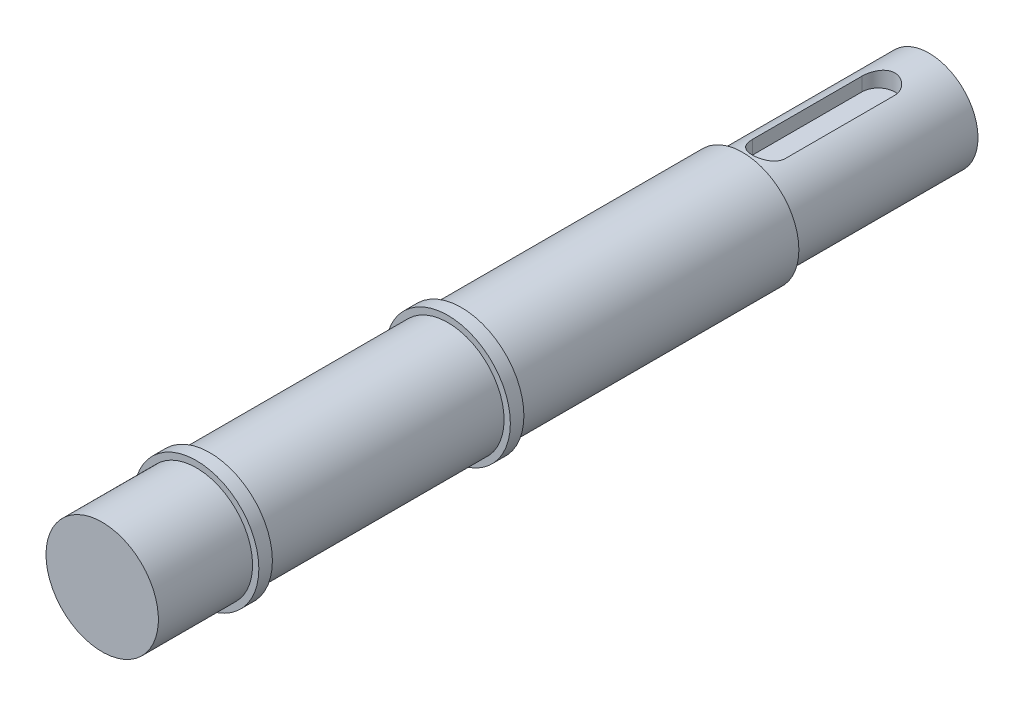
SolidWorks part; units mm, degrees
ref_plane "前视基准面" through (0, 0, 0) normal (0, 0, 1) x (1, 0, 0)
ref_plane "上视基准面" through (0, 0, 0) normal (0, 1, 0) x (1, 0, 0)
ref_plane "右视基准面" through (0, 0, 0) normal (1, 0, 0) x (0, 0, -1)
sketch "草图1" plane through (0, 0, 0) normal (0, 0, 1) x (1, 0, 0)
  circle A0 centre (0, 0) radius 9.45
  circle A1 centre (0, 0) radius 7.4
  circle A2 centre (0, 0) radius 2.7664
  circle A3 centre (0, 0) radius 8.5
  circle A4 centre (0, 0) radius 8.5
  dimension "D1" = 18.9
  dimension "D2" = 14.8
  dimension "D3" = 17
  dimension "D4" = 5.5328
  dimension "D5" = 17
extrude "凸台-拉伸1" add sketch "草图1" along normal blind 28.2 contours A1
extrude "凸台-拉伸2" add sketch "草图1<5>" along normal blind 42.55 from offset 28.2 contours A3
sketch "草图1<5>" plane through (0, 0, 0) normal (0, 0, 1) x (1, 0, 0) same geometry as "草图1"
extrude "凸台-拉伸3" add sketch "草图1<7>" along normal blind 2.05 from offset 70.75 contours A0
sketch "草图1<7>" plane through (0, 0, 0) normal (0, 0, 1) x (1, 0, 0) same geometry as "草图1"
extrude "凸台-拉伸4" add sketch "草图1<8>" along normal blind 2.05 from offset 108.8 separate body contours A0
sketch "草图1<8>" plane through (0, 0, 0) normal (0, 0, 1) x (1, 0, 0) same geometry as "草图1"
extrude "凸台-拉伸5" add sketch "草图1<9>" along normal blind 36 from offset 72.8 contours A4
sketch "草图1<9>" plane through (0, 0, 0) normal (0, 0, 1) x (1, 0, 0) same geometry as "草图1"
extrude "凸台-拉伸6" add sketch "草图1<10>" along normal blind 14.25 from offset 110.85 contours A3
sketch "草图1<10>" plane through (0, 0, 0) normal (0, 0, 1) x (1, 0, 0) same geometry as "草图1"
sketch "草图11" plane through (0, 0, 0) normal (0, 1, 0) x (1, 0, 0)
  line L0 (0, -7.68) -> (0, -24.22) construction
  line L1 (2.5, -7.68) -> (2.5, -24.22)
  line L2 (-2.5, -7.68) -> (-2.5, -24.22)
  arc A0 (2.5, -7.68) -> (-2.5, -7.68) centre (0, -7.68) ccw
  arc A1 (-2.5, -24.22) -> (2.5, -24.22) centre (0, -24.22) ccw
  point P2 (0, -15.95)
  point P8 (0, -5.18)
  point P9 (0, -26.72)
  dimension "D1" = 5.18
  dimension "D2" = 5
  dimension "D3" = 21.54
extrude "切除-拉伸1" cut sketch "草图11" against normal blind 2.5 from offset 7.4
sketch "草图8" plane through (0, 0, 0) normal (0, 0, 1) x (1, 0, 0)
  spline S0 degree 4 poles (11.2763, 0) (11.2815, 0.0001) (11.2959, 0.0006) (11.3231, 0.0026) (11.3674, 0.0073) (11.4237, 0.0155) (11.4962, 0.0286) (11.5812, 0.0473) (11.6741, 0.0711) (11.7745, 0.1005) (11.874, 0.1331) (11.9726, 0.1684) (12.0702, 0.2063) (12.1875, 0.2551) (12.3271, 0.318) (12.4883, 0.3976) (12.6687, 0.495) (12.8498, 0.6019) (13.0256, 0.7132) (13.2003, 0.8326) (13.3672, 0.9531) (13.5373, 1.0851) (13.6926, 1.2106) (13.8627, 1.3587) (13.9988, 1.4805) (14.174, 1.6489) (14.2762, 1.7507) (14.3942, 1.8725) (14.4457, 1.928) (14.4775, 1.9621) knots 0 0 0 0 0 0.005377 0.015084 0.028532 0.04661 0.064855 0.092111 0.119476 0.146842 0.174209 0.201575 0.228941 0.256307 0.307035 0.361767 0.4165 0.471232 0.525964 0.580697 0.635429 0.690161 0.744894 0.799626 0.854358 0.909091 0.954545 1 1 1 1 1 construction
  spline S1 degree 4 poles (11.2763, 0) (11.2815, 0.0001) (11.2959, 0.0006) (11.3231, 0.0026) (11.3674, 0.0073) (11.4237, 0.0155) (11.4962, 0.0286) (11.5812, 0.0473) (11.6741, 0.0711) (11.7745, 0.1005) (11.874, 0.1331) (11.9726, 0.1684) (12.0702, 0.2063) (12.1875, 0.2551) (12.3271, 0.318) (12.4883, 0.3976) (12.6687, 0.495) (12.8498, 0.6019) (13.0256, 0.7132) (13.2003, 0.8326) (13.3672, 0.9531) (13.5373, 1.0851) (13.6926, 1.2106) (13.8627, 1.3587) (13.9988, 1.4805) (14.1361, 1.6124) (14.2023, 1.6775) (14.236, 1.7111) knots 0 0 0 0 0 0.005377 0.015084 0.028532 0.04661 0.064855 0.092111 0.119476 0.146842 0.174209 0.201575 0.228941 0.256307 0.307035 0.361767 0.4165 0.471232 0.525964 0.580697 0.635429 0.690161 0.744894 0.799626 0.854358 0.909091 0.909091 0.909091 0.909091 0.909091
sketch "草图6" plane through (0, 0, 0) normal (0, 0, 1) x (1, 0, 0)
  line L0 (0, 0) -> (14.6649, 2.1549) construction
  circle A0 centre (0, 0) radius 9.45 construction
  circle A1 centre (0, 0) radius 7.4
  circle A2 centre (0, 0) radius 2.7664
  circle A3 centre (0, 0) radius 8.5
  circle A4 centre (0, 0) radius 12 construction
  circle A5 centre (0, 0) radius 9.5 construction
  circle A6 centre (0, 0) radius 11.2763
  circle A7 centre (0, 0) radius 14
  arc A8 (11.7916, 0.1066) -> (11.2614, -0.5791) centre (12.0204, -0.6181) ccw
  spline S0 degree 4 poles (-14.1478, 1999.7229) (9.4338, 23.2482) (10.0756, 0.3378) (10.7357, -0.0602) (11.3674, 0.0073) (11.4237, 0.0155) (11.4962, 0.0286) (11.5812, 0.0473) (11.6741, 0.0711) (11.7745, 0.1005) (11.874, 0.1331) (11.9726, 0.1684) (12.0702, 0.2063) (12.1875, 0.2551) (12.3271, 0.318) (12.4883, 0.3976) (12.6687, 0.495) (12.8498, 0.6019) (13.0256, 0.7132) (13.2003, 0.8326) (13.3672, 0.9531) (13.5373, 1.0851) (13.6926, 1.2106) (13.8627, 1.3587) (14.6115, 2.0283) (17.0468, 4.6575) (-19.889, -31.9248) (1427.9155, 1416.391) knots -0.617559 -0.617559 -0.617559 -0.617559 -0.617559 0.005377 0.015084 0.028532 0.04661 0.064855 0.092111 0.119476 0.146842 0.174209 0.201575 0.228941 0.256307 0.307035 0.361767 0.4165 0.471232 0.525964 0.580697 0.635429 0.690161 0.744894 0.799626 0.854358 1.894324 1.894324 1.894324 1.894324 1.894324 only from (11.2763, 0) to (14.236, 1.7111) construction
  spline S1 degree 4 poles (11.7916, 0.1066) (11.8247, 0.117) (11.8825, 0.1361) (11.9646, 0.1653) (12.0702, 0.2063) (12.1875, 0.2551) (12.3271, 0.318) (12.4883, 0.3976) (12.6687, 0.495) (12.8498, 0.6019) (13.0256, 0.7132) (13.2003, 0.8326) (13.3672, 0.9531) (13.5373, 1.0851) (13.6917, 1.2099) (13.8183, 1.3201) (13.8915, 1.3848) (13.928, 1.4178) knots 0.137896 0.137896 0.137896 0.137896 0.137896 0.174209 0.201575 0.228941 0.256307 0.307035 0.361767 0.4165 0.471232 0.525964 0.580697 0.635429 0.690161 0.744894 0.798429 0.798429 0.798429 0.798429 0.798429
  point P2 (33.674, -7.0096)
  point P11 (12.1017, 0.1374)
  point P12 (11.8725, 1.7446)
  point P19 (13.928, 1.4178)
  point P23 (11.9987, 0.1788)
  dimension "D10" = 0.76
  dimension "D9" = 1.5708
  dimension "D1" = 18.9
  dimension "D2" = 14.8
  dimension "D3" = 17
  dimension "D4" = 5.5328
  dimension "D6" = 28
  dimension "D7" = 19
  dimension "D8" = 22.5526
  dimension "D5" = 24
sketch "草图5" plane through (0, 0, 0) normal (0, 0, 1) x (1, 0, 0)
  spline S0 degree 4 poles (11.2763, 0) (11.2815, 0.0001) (11.2959, 0.0006) (11.3231, 0.0026) (11.3674, 0.0073) (11.4237, 0.0155) (11.4962, 0.0286) (11.5812, 0.0473) (11.6741, 0.0711) (11.7745, 0.1005) (11.874, 0.1331) (11.9726, 0.1684) (12.0702, 0.2063) (12.1875, 0.2551) (12.3271, 0.318) (12.4883, 0.3976) (12.6687, 0.495) (12.8498, 0.6019) (13.0256, 0.7132) (13.2003, 0.8326) (13.3672, 0.9531) (13.5373, 1.0851) (13.6926, 1.2106) (13.8627, 1.3587) (13.9988, 1.4805) (14.174, 1.6489) (14.2762, 1.7507) (14.3942, 1.8725) (14.4457, 1.928) (14.4775, 1.9621) knots 0 0 0 0 0 0.005377 0.015084 0.028532 0.04661 0.064855 0.092111 0.119476 0.146842 0.174209 0.201575 0.228941 0.256307 0.307035 0.361767 0.4165 0.471232 0.525964 0.580697 0.635429 0.690161 0.744894 0.799626 0.854358 0.909091 0.954545 1 1 1 1 1 construction
  spline S1 degree 4 poles (11.2763, 0) (11.2815, 0.0001) (11.2959, 0.0006) (11.3231, 0.0026) (11.3674, 0.0073) (11.4237, 0.0155) (11.4962, 0.0286) (11.5812, 0.0473) (11.6741, 0.0711) (11.7745, 0.1005) (11.874, 0.1331) (11.9726, 0.1684) (12.0702, 0.2063) (12.1875, 0.2551) (12.3271, 0.318) (12.4883, 0.3976) (12.6687, 0.495) (12.8498, 0.6019) (13.0256, 0.7132) (13.2003, 0.8326) (13.3672, 0.9531) (13.5373, 1.0851) (13.6926, 1.2106) (13.8627, 1.3587) (13.9988, 1.4805) (14.1361, 1.6124) (14.2023, 1.6775) (14.236, 1.7111) knots 0 0 0 0 0 0.005377 0.015084 0.028532 0.04661 0.064855 0.092111 0.119476 0.146842 0.174209 0.201575 0.228941 0.256307 0.307035 0.361767 0.4165 0.471232 0.525964 0.580697 0.635429 0.690161 0.744894 0.799626 0.854358 0.909091 0.909091 0.909091 0.909091 0.909091
sketch "草图3" plane through (0, 0, 0) normal (0, 0, 1) x (1, 0, 0)
  line L0 (0, 0) -> (61.0042, 2.8371) construction
  circle A0 centre (0, 0) radius 9.45
  circle A1 centre (0, 0) radius 7.4
  circle A2 centre (0, 0) radius 2.7664
  circle A3 centre (0, 0) radius 8.5
  circle A4 centre (0, 0) radius 12 construction
  circle A5 centre (0, 0) radius 11.2763 construction
  circle A6 centre (0, 0) radius 9.5
  circle A7 centre (0, 0) radius 14
  arc A8 (7.3504, 8.209) -> (6.3645, 7.0529) centre (6.8736, 7.6172) ccw
  arc A9 (8.0806, -7.4914) -> (6.9916, -6.4318) centre (7.5509, -6.9463) cw
  spline S1 degree 4 poles (7.7594, 9.7771) (7.5252, 9.5776) (7.2915, 9.3775) (7.0583, 9.177) (6.8255, 8.976) knots 0 0 0 0 0 0.000671 0.000671 0.000671 0.000671 0.000671
  spline S2 degree 4 poles (7.3504, 8.209) (7.4327, 8.2274) (7.621, 8.2715) (7.9139, 8.3474) (8.3089, 8.4633) (8.7235, 8.5989) (9.1343, 8.7461) (9.541, 8.9039) (9.9236, 9.0632) (10.2029, 9.1864) (10.3814, 9.268) (10.4605, 9.3047) knots 0.070939 0.070939 0.070939 0.070939 0.070939 0.092111 0.119476 0.146842 0.174209 0.201575 0.228941 0.256307 0.27819 0.27819 0.27819 0.27819 0.27819
  spline S3 degree 4 poles (8.0806, -7.4914) (8.1642, -7.502) (8.3559, -7.5285) (8.6545, -7.5769) (9.0585, -7.6556) (9.484, -7.7521) (9.9066, -7.8606) (10.3262, -7.9799) (10.722, -8.103) (11.0115, -8.1998) (11.1968, -8.2645) (11.2789, -8.2937) knots 0.070939 0.070939 0.070939 0.070939 0.070939 0.092111 0.119476 0.146842 0.174209 0.201575 0.228941 0.256307 0.27819 0.27819 0.27819 0.27819 0.27819
  point P12 (11.987, 0.5575)
  point P14 (11.9572, -1.013)
  dimension "D1" = 18.9
  dimension "D2" = 14.8
  dimension "D3" = 17
  dimension "D4" = 5.5328
  dimension "D5" = 28
  dimension "D6" = 19
  dimension "D7" = 22.5526
  dimension "D8" = 24
  dimension "D10" = 0.76
  dimension "D9" = 1.5708
equation "\"m\"= 2'模数"
equation "\"z\"= 12'齿数"
equation "\"a\"= 20'压力角"
equation "\"d\"= \"m\" * \"z\"'分度圆直径"
equation "\"da\"= ( \"z\" + 2 ) * \"m\"'齿顶圆直径"
equation "\"df\"= ( \"z\" - 2.5 ) * \"m\"'齿根圆直径"
equation "\"db\"= \"m\" * \"z\" * cos ( \"a\" )'基圆直径"
equation "\"rb\"= \"db\" / 2'基圆半径"
equation "\"s\" = 0.5 * PI * \"m\"'分度圆齿厚"
equation "\"r\"= 0.38 * \"m\"'齿根圆角"
equation "\"D5@草图3\"=\"da\""
equation "\"D6@草图3\"=\"df\""
equation "\"D7@草图3\"=\"db\""
equation "\"D8@草图3\"=\"d\""
equation "\"D9@草图3\"=\"s\"/2"
equation "\"D10@草图3\"=\"r\""
equation "\"D6@草图6\"=\"da\""
equation "\"D7@草图6\"=\"df\""
equation "\"D8@草图6\"=\"db\""
equation "\"D5@草图6\"=\"d\""
equation "\"D9@草图6\"=\"s\"/2"
equation "\"D10@草图6\"=\"r\""
